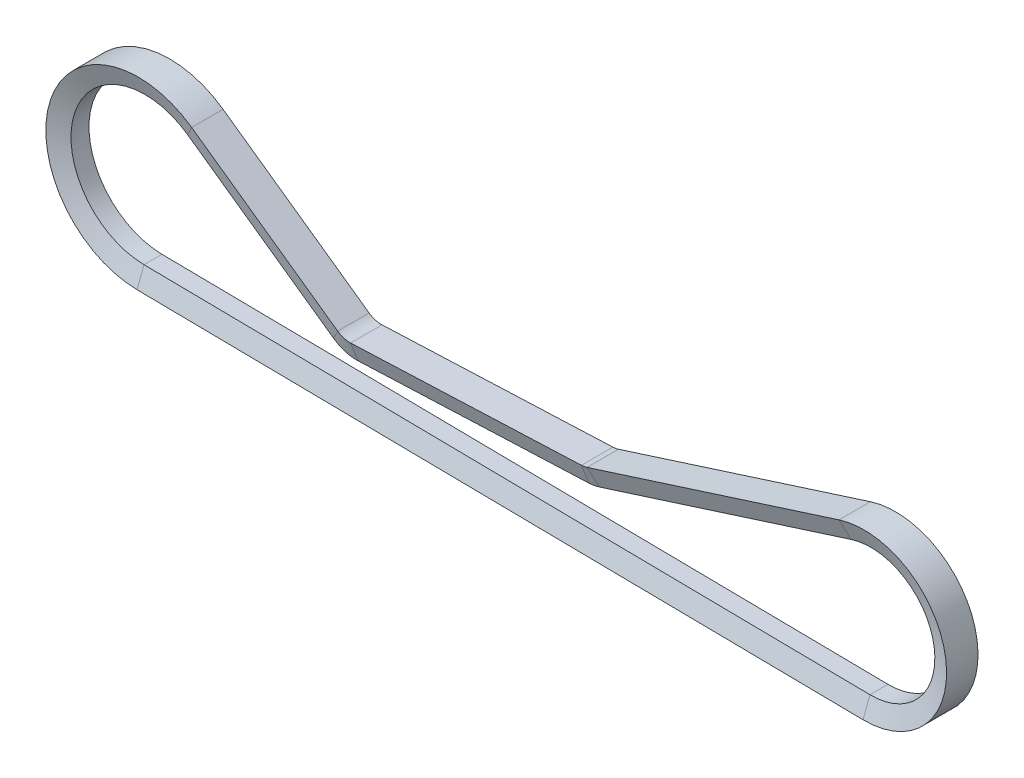
SolidWorks part; units mm, degrees
ref_plane "Front Plane" through (0, 0, 0) normal (0, 0, 1) x (1, 0, 0)
ref_plane "Top Plane" through (0, 0, 0) normal (0, 1, 0) x (1, 0, 0)
ref_plane "Right Plane" through (0, 0, 0) normal (1, 0, 0) x (0, 0, -1)
sketch "Sketch2" plane through (0, 0, 0) normal (0, 0, 1) x (1, 0, 0)
  line L0 (0, 0) -> (1, 0) construction
  line L1 (0, 0) -> (0, 1) construction
  line L12 (-0.3246, -24.9979) -> (-220.2856, -22.1414)
  line L14 (-203.7481, 28.7124) -> (-159.4936, -2.6039)
  line L15 (-155.5638, -3.7651) -> (-85.6233, -0.8799)
  line L16 (-83.952, -0.5839) -> (-7.6104, 23.8135)
  arc A4 (-220.2856, -22.1414) -> (-203.7481, 28.7124) centre (-219.922, 5.8562) cw
  arc A7 (-7.6104, 23.8135) -> (-0.3246, -24.9979) centre (0, 0) cw
  arc A8 (-159.4936, -2.6039) -> (-155.5638, -3.7651) centre (-155.8256, 2.5795) ccw
  arc A9 (-85.6233, -0.8799) -> (-83.952, -0.5839) centre (-85.885, 5.4647) ccw
ref_plane "Plane4" through (-7.6104, 23.8135, 0) normal (0.9525, 0.3044, 0) x (0.3044, -0.9525, 0)
sketch "Sketch3" plane through (-7.6104, 23.8135, 0) normal (0.9525, 0.3044, 0) x (0.3044, -0.9525, 0)
  line L0 (0, -4.7625) -> (0, 4.7625)
  line L1 (0, -4.7625) -> (5.588, -2.7286)
  line L2 (5.588, -2.7286) -> (5.588, 2.7286)
  line L3 (5.588, 2.7286) -> (0, 4.7625)
  line L4 (0, 0) -> (5.588, 0) construction
  dimension "D1" = 9.525
  dimension "D2" = 5.588
  dimension "D3" = 40
sweep "Sweep1" add profiles "Sketch3" path "Sketch2"
